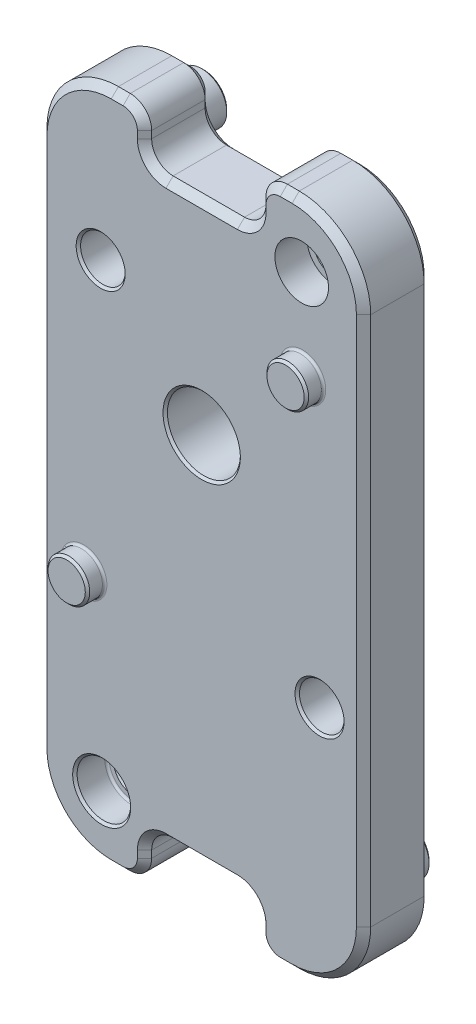
SolidWorks part; units mm, degrees
ref_plane "Front" through (0, 0, 0) normal (0, 0, 1) x (1, 0, 0)
ref_plane "Top" through (0, 0, 0) normal (0, 1, 0) x (1, 0, 0)
ref_plane "Right" through (0, 0, 0) normal (1, 0, 0) x (0, 0, -1)
sketch "Sketch2" plane through (0, 0, 0) normal (0, 0, 1) x (1, 0, 0)
  line L0 (0, 15.3416) -> (0, -37.3507) construction
  line L1 (14.3891, -37.3507) -> (-14.3891, -37.3507)
  line L2 (14.3891, -37.3507) -> (14.3891, 22.4818)
  line L4 (-14.3891, -37.3507) -> (-14.3891, 22.4818)
  line L5 (-15.4933, 0) -> (15.4933, 0) construction
  line L6 (-14.3891, 15.3416) -> (14.3891, 15.3416) construction
  line L7 (-14.3891, 22.4818) -> (14.3891, 22.4818)
  line L8 (-14.3891, -28.0416) -> (14.3891, -28.0416) construction
  line L9 (-14.3891, -31.8516) -> (14.3891, -31.8516) construction
  line L10 (-8.89, 16.9827) -> (-8.89, -31.8516) construction
  line L11 (8.89, 16.9827) -> (8.89, -31.8516) construction
  circle A1 centre (0, 0) radius 3.2385
  arc A2 (-15.4933, 0) -> (15.4933, 0) centre (0, -0.1524) cw construction
  arc A3 (-19.3034, 0) -> (19.3034, 0) centre (0, -0.1524) cw construction
  circle A5 centre (8.89, 16.9827) radius 1.5875
  circle A6 centre (-8.89, -31.8516) radius 1.5875
  point P10 (0, 0)
  dimension "D3" = 15.3416
  dimension "D2" = 15.494
  dimension "D4" = 6.477
  dimension "D6" = 3.81
  dimension "D7" = 3.175
  dimension "D10" = 5.4991
  dimension "D1" = 28.7782
  dimension "D5" = 43.3832
  dimension "D8" = 5.4991
  dimension "D9" = 5.4991
  dimension "D11" = 3.81
  dimension "D12" = 5.4991
extrude "Boss-Extrude1" add sketch "Sketch2" along normal blind 6.0198
sketch "Sketch3" plane through (0, 0, 6.0198) normal (0, 0, 1) x (1, 0, 0)
  circle A0 centre (-8.89, -31.8516) radius 2.3813
  circle A2 centre (8.89, 16.9827) radius 2.3812
  dimension "D1" = 4.7625
extrude "Cut-Extrude1_Counter-sink" cut sketch "Sketch3" against normal blind 2.8448
sketch "Sketch4" plane through (0, 0, 0) normal (0, 0, -1) x (-1, 0, 0)
  line L0 (-8.89, 16.9827) -> (14.3891, 16.9827) construction
  line L1 (14.3891, 22.4818) -> (14.3891, -37.3507) construction
  line L2 (8.89, -31.8516) -> (-14.3891, -31.8516) construction
  line L3 (-14.3891, -37.3507) -> (-14.3891, 22.4818) construction
  circle A0 centre (-8.9916, -31.8516) radius 2.2225
  circle A1 centre (8.9916, 16.9827) radius 2.2225
  dimension "D1" = 4.445
  dimension "D2" = 5.3975
  dimension "D3" = 5.3975
extrude "Boss-Extrude2_BackPegs" add sketch "Sketch4" along normal blind 3.175
sketch "Sketch5" plane through (0, 0, 6.0198) normal (0, 0, 1) x (1, 0, 0)
  line L0 (-10.4775, 22.4818) -> (-10.4775, -37.3507) construction
  line L1 (14.3891, 22.4818) -> (-14.3891, 22.4818) construction
  line L2 (-14.3891, -37.3507) -> (14.3891, -37.3507) construction
  line L3 (10.4775, 22.4818) -> (10.4775, -37.3507) construction
  line L4 (-10.4775, -7.4344) -> (10.4775, -7.4344) construction
  line L5 (0, 0) -> (0, -7.4344) construction
  line L6 (-14.3891, 22.4818) -> (-14.3891, -37.3507) construction
  circle A0 centre (-10.4775, -15.748) radius 1.9812 construction
  circle A1 centre (10.4775, -15.748) radius 1.9812
  circle A2 centre (0, 0) radius 12.7 construction
  circle A3 centre (-8.9789, 8.9816) radius 1.9812
  circle A4 centre (8.9789, 8.9816) radius 1.9812 construction
  dimension "D2" = 3.9624
  dimension "D3" = 25.4
  dimension "D1" = 20.955
  dimension "D4" = 5.4102
  dimension "D5" = 15.748
extrude "Cut-Extrude2_EncoderScrewHoles" cut sketch "Sketch5" against normal through all
sketch "Sketch6" plane through (0, 0, 6.0198) normal (0, 0, 1) x (1, 0, 0)
  line L0 (-10.4775, 22.4818) -> (-10.4775, -37.3507) construction
  line L1 (10.4775, 22.4818) -> (10.4775, -37.3507) construction
  line L2 (-10.4775, -7.4344) -> (10.4775, -7.4344) construction
  line L3 (0, 0) -> (0, -7.4344) construction
  line L4 (14.3891, 22.4818) -> (-14.3891, 22.4818) construction
  line L5 (-14.3891, -37.3507) -> (14.3891, -37.3507) construction
  line L6 (-14.3891, 22.4818) -> (-14.3891, -37.3507) construction
  circle A0 centre (-10.4775, -15.748) radius 1.8542
  circle A1 centre (10.4775, -15.748) radius 1.8542 construction
  circle A2 centre (0, 0) radius 12.7 construction
  circle A3 centre (-8.9789, 8.9816) radius 1.8542 construction
  circle A4 centre (8.9789, 8.9816) radius 1.8542
  dimension "D2" = 3.7084
  dimension "D3" = 25.4
  dimension "D1" = 20.955
  dimension "D4" = 15.748
  dimension "D5" = 5.4102
extrude "Boss-Extrude3_EncoderPegs" add sketch "Sketch6" along normal blind 1.524
ref_axis "Axis1" through (0, 0, 36.0066) along (0, 0, -1)
ref_plane "Plane1" through (0, 0, 0) normal (0, 1, 0) x (1, 0, 0)
sketch "Sketch8" plane through (0, 0, 0) normal (0, 1, 0) x (1, 0, 0)
  line L0 (0, 7.9624) -> (0, -6.0198) construction
  line L1 (-14.3891, -6.0198) -> (14.3891, -6.0198) construction
  line L2 (-2.3812, 0) -> (-2.3812, 3.175)
  line L3 (-14.3891, 0) -> (14.3891, 0) construction
  line L4 (-2.3812, 3.175) -> (-3.9687, 3.175)
  line L5 (-3.9687, 3.175) -> (-3.9687, 0.1984)
  line L6 (-2.3812, 0) -> (-4.1672, 0)
  arc A0 (-3.9687, 0.1984) -> (-4.1672, 0) centre (-4.1672, 0.1984) cw
  dimension "D1" = 0.1984
  dimension "D2" = 3.175
  dimension "D3" = 1.5875
  dimension "D4" = 2.3813
revolve "Revolve1" [suppressed] add sketch "Sketch8" angle 360 about L0
sketch "Sketch7" plane through (0, 0, 0) normal (0, 0, -1) x (-1, 0, 0)
  line L0 (0, 22.4818) -> (0, -37.3507) construction
  line L1 (-14.3891, 22.4818) -> (14.3891, 22.4818) construction
  line L2 (14.3891, -37.3507) -> (-14.3891, -37.3507) construction
  line L3 (-14.3891, -11.9507) -> (14.3891, -11.9507) construction
  circle A0 centre (0, -11.9507) radius 3.9688
  dimension "D1" = 7.9375
  dimension "D2" = 25.4
extrude "Boss-Extrude4" add sketch "Sketch7" along normal blind 3.175
sketch "Sketch10" plane through (0, 0, 0) normal (0, 0, -1) x (-1, 0, 0)
  line L0 (-8.89, 16.9827) -> (-8.89, -37.3507) construction
  line L1 (-14.3891, 22.4818) -> (14.3891, 22.4818) construction
  line L2 (14.3891, -37.3507) -> (-14.3891, -37.3507) construction
  line L3 (0, 22.4818) -> (0, -37.3507) construction
  line L4 (-8.89, 16.9827) -> (-8.89, 22.4818) construction
  line L6 (-5.08, 22.4818) -> (5.08, 22.4818)
  line L7 (-5.08, 22.4818) -> (-5.08, 18.0368)
  line L8 (-5.08, 18.0368) -> (5.08, 18.0368)
  line L9 (5.08, 22.4818) -> (5.08, 18.0368)
  point P15 (0, 18.0368)
  dimension "D1" = 4.445
  dimension "D2" = 3.81
extrude "Cut-Extrude3" cut sketch "Sketch10" against normal through all
ref_plane "Midplane" through (0, -7.4344, 0) normal (0, -1, 0) x (-1, 0, 0)
mirror "Mirror1" about plane through (0, -7.4344, 0) normal (0, -1, 0) of "Cut-Extrude3"
fillet "Fillet1_0.25" radius 6.35 4 edges at (-14.3891, -37.3507, 3.0099) (14.3891, -37.3507, 3.0099) (14.3891, 22.4818, 3.0099) (-14.3891, 22.4818, 3.0099)
fillet "Fillet5" radius 1.905 4 edges at (-5.08, 22.4818, 3.0099) (5.08, 22.4818, 3.0099) (5.08, -37.3507, 3.0099) (-5.08, -37.3507, 3.0099)
fillet "Fillet4_0.075" radius 1.905 4 edges at (-5.08, 18.0368, 3.0099) (5.08, 18.0368, 3.0099) (-5.08, -32.9057, 3.0099) (5.08, -32.9057, 3.0099)
fillet "Fillet3_1/128" radius 0.1984 6 edges at (-6.5088, -31.8516, 3.175) (6.7691, -31.8516, 0) (-11.2141, 16.9827, 0) (7.1247, 8.9816, 6.0198) (-12.3317, -15.748, 6.0198) (-3.9688, -11.9507, 0)
chamfer "Chamfer1_0.25" distance 0.635 angle 45 22 edges at (-12.5292, -35.4908, 6.0198) (-14.3891, -7.4344, 6.0198) (-12.5292, 20.6219, 6.0198) (-12.5292, -35.4908, 0) (-14.3891, -7.4344, 0) (-12.5292, 20.6219, 0) (-7.512, 22.4818, 0) (-7.512, 22.4818, 6.0198) (5.08, 20.2593, 0) (4.522, 18.5948, 0) (0, 18.0368, 0) (-4.522, 18.5948, 0) (-5.08, 20.2593, 0) (5.08, 20.2593, 6.0198) (4.522, 18.5948, 6.0198) (0, 18.0368, 6.0198) (-4.522, 18.5948, 6.0198) (-5.08, 20.2593, 6.0198) (5.638, 21.9239, 0) (-5.638, 21.9239, 0) (5.638, 21.9239, 6.0198) (-5.638, 21.9239, 6.0198)
chamfer "Chamfer2_1/128" distance 0.1984 angle 45 14 edges at (-7.3025, -31.8516, 3.175) (3.2385, 0, 6.0198) (10.4775, 16.9827, 0) (-6.9977, 8.9816, 6.0198) (-10.9601, 8.9816, 0) (12.4587, -15.748, 6.0198) (8.4963, -15.748, 0) (6.7691, -31.8516, -3.175) (-11.2141, 16.9827, -3.175) (-8.6233, -15.748, 7.5438) (10.8331, 8.9816, 7.5438) (-7.3025, -31.8516, 0) (-6.5088, -31.8516, 6.0198) (10.4775, 16.9827, 3.175)
chamfer "Chamfer3_1/64" distance 0.3969 angle 45 1 edges at (-3.9688, -11.9507, -3.175)
equation "\"D2@Sketch4\"=(\"D1@Sketch4\"/2)+.125"
equation "\"D3@Sketch4\"=\"D2@Sketch4\""
